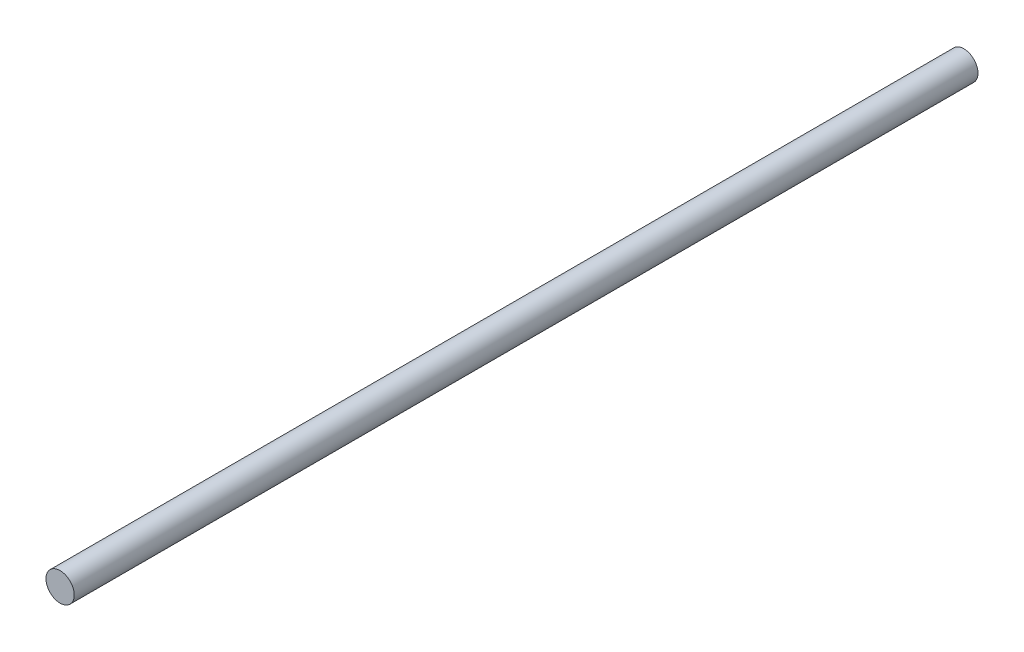
SolidWorks part; units mm, degrees
ref_plane "Front Plane" through (0, 0, 0) normal (0, 0, 1) x (1, 0, 0)
ref_plane "Top Plane" through (0, 0, 0) normal (0, 1, 0) x (1, 0, 0)
ref_plane "Right Plane" through (0, 0, 0) normal (1, 0, 0) x (0, 0, -1)
sketch "Sketch1" plane through (0, 0, 0) normal (0, 0, 1) x (1, 0, 0)
  circle A0 centre (0, 0) radius 0.3969
  dimension "D1" = 0.7937
extrude "Boss-Extrude1" add sketch "Sketch1" along normal blind 25.4 contours A0
